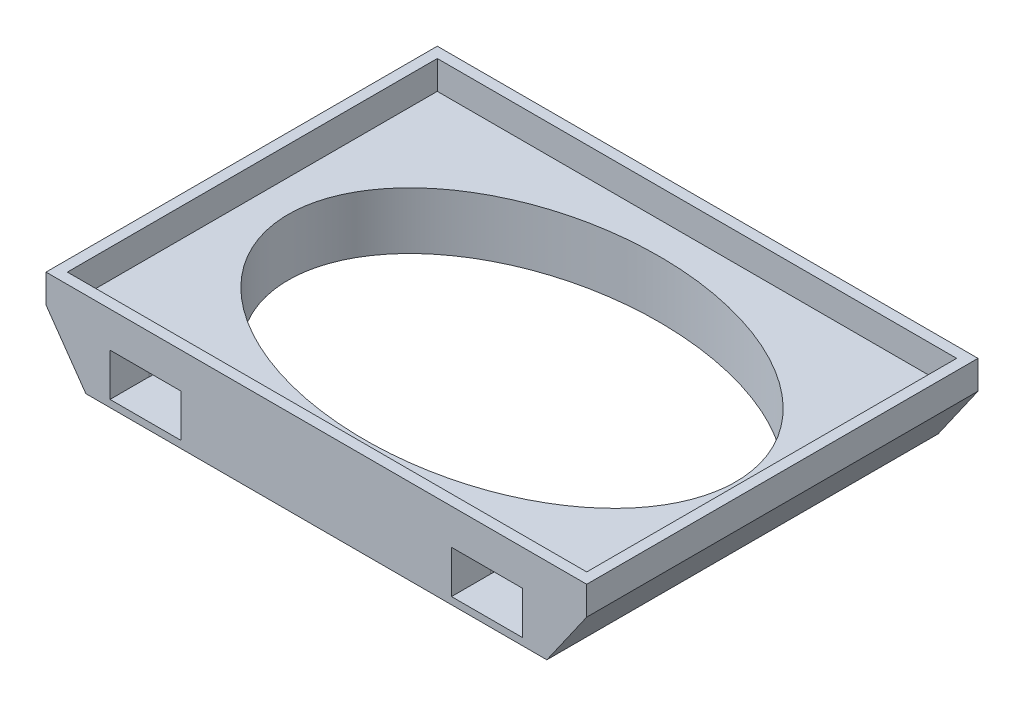
SolidWorks part; units mm, degrees
ref_plane "Front Plane" through (0, 0, 0) normal (0, 0, 1) x (1, 0, 0)
ref_plane "Top Plane" through (0, 0, 0) normal (0, 1, 0) x (1, 0, 0)
ref_plane "Right Plane" through (0, 0, 0) normal (1, 0, 0) x (0, 0, -1)
sketch "Sketch1" plane through (0, 0, 0) normal (0, 1, 0) x (1, 0, 0)
  line L0 (-36.5297, 0) -> (34.0127, 0) construction
  line L1 (0, -19.8975) -> (0, 26.8361) construction
  line L3 (-19, -13.75) -> (19, -13.75)
  line L4 (-19, -13.75) -> (-19, 13.75)
  line L5 (-19, 13.75) -> (19, 13.75)
  line L6 (19, -13.75) -> (19, 13.75)
  dimension "D1" = 27.5
  dimension "D2" = 38
  dimension "D3" = 13.75
  dimension "D4" = 19
extrude "Boss-Extrude1" add sketch "Sketch1" against normal blind 6
sketch "Sketch2" plane through (0, 0, 0) normal (0, 1, 0) x (1, 0, 0)
  line L0 (-19, 13.75) -> (-19, -13.75) construction
  line L1 (-18.25, 13) -> (18.25, 13)
  line L2 (-18.25, 13) -> (-18.25, -13)
  line L3 (-18.25, -13) -> (18.25, -13)
  line L4 (18.25, 13) -> (18.25, -13)
  line L5 (19, -13.75) -> (19, 13.75) construction
  line L6 (19, 13.75) -> (-19, 13.75) construction
  line L7 (-19, -13.75) -> (19, -13.75) construction
  dimension "D1" = 0.75
  dimension "D2" = 0.75
  dimension "D3" = 0.75
  dimension "D4" = 0.75
extrude "Cut-Extrude1" cut sketch "Sketch2" against normal blind 2
sketch "Sketch3" plane through (0, -2, 0) normal (0, 1, 0) x (1, 0, 0)
  line L14 (-19, 13.75) -> (-19, -13.75) construction
  line L15 (-19, -13.75) -> (19, -13.75) construction
  ellipse E0 centre (0, 0) end of major axis (16, -0.498) minor radius 10.7552
  dimension "D1" = 3
  dimension "D2" = 3
extrude "Cut-Extrude2" cut sketch "Sketch3" against normal through all both and the other way through all
sketch "Sketch4" plane through (0, 0, 0) normal (0, 1, 0) x (1, 0, 0)
  line L0 (-25.2485, 0) -> (37.2083, 0) construction
  line L1 (0, -20.0379) -> (0, 20.8772) construction
ref_axis "Axis1" through (0, 0, 20.0379) along (0, 0, -1)
ref_axis "Axis2" through (-25.2485, 0, 0) along (1, 0, 0)
sketch "Sketch7" plane through (0, -6, 0) normal (0, 1, 0) x (1, 0, 0)
  line L5 (-19, -13.75) -> (-9, -13.75)
  line L6 (-19, -13.75) -> (-19, -4.736)
  line L7 (-19, -4.736) -> (-9, -4.736)
  line L8 (-9, -13.75) -> (-9, -4.736)
  line L9 (-19, 13.75) -> (-9, 13.75)
  line L10 (-19, 13.75) -> (-19, 3.75)
  line L11 (-19, 3.75) -> (-9, 3.75)
  line L12 (-9, 13.75) -> (-9, 3.75)
  line L13 (19, 13.75) -> (9, 13.75)
  line L14 (19, 13.75) -> (19, 3.75)
  line L15 (19, 3.75) -> (9, 3.75)
  line L16 (9, 13.75) -> (9, 3.75)
  line L17 (19, -13.75) -> (9, -13.75)
  line L18 (19, -13.75) -> (19, -3.75)
  line L19 (19, -3.75) -> (9, -3.75)
  line L20 (9, -13.75) -> (9, -3.75)
  dimension "D1" = 10
  dimension "D2" = 10
  dimension "D3" = 10
  dimension "D4" = 10
  dimension "D5" = 10
  dimension "D6" = 10
  dimension "D7" = 10
extrude "Cut-Extrude3" [suppressed] cut sketch "Sketch7" along normal blind 1
ref_plane "Plane1" through (0, -4, 0) normal (0, -1, 0) x (-1, 0, 0)
sketch "Sketch8" plane through (0, -4, 0) normal (0, -1, 0) x (-1, 0, 0)
  line L0 (-14.5, 11) -> (-14.5, 23.5627)
  line L1 (-14.5, 23.5627) -> (-9.5, 23.5627)
  line L2 (-9.5, 23.5627) -> (-9.5, 11)
  line L3 (-14.5, 11) -> (-9.5, 11) construction
  line L4 (0, -20.0379) -> (0, 20.8772) construction
  line L5 (25.2485, 0) -> (-37.2083, 0) construction
  line L6 (0, 39.7599) -> (0, -34.6026) construction
  line L7 (-51.5772, 0) -> (38.0826, 0) construction
  line L8 (9.5, 23.5627) -> (9.5, 11)
  line L9 (14.5, 11) -> (14.5, 23.5627)
  line L10 (14.5, 23.5627) -> (9.5, 23.5627)
  line L11 (14.5, -11) -> (14.5, -23.5627)
  line L12 (14.5, -23.5627) -> (9.5, -23.5627)
  line L13 (9.5, -23.5627) -> (9.5, -11)
  line L14 (-9.5, -23.5627) -> (-9.5, -11)
  line L15 (-14.5, -23.5627) -> (-9.5, -23.5627)
  line L16 (-14.5, -11) -> (-14.5, -23.5627)
  arc A1 (14.5, 11) -> (9.5, 11) centre (12, 11) cw
  arc A2 (-14.5, 11) -> (-9.5, 11) centre (-12, 11) ccw
  arc A3 (14.5, -11) -> (9.5, -11) centre (12, -11) ccw
  arc A4 (-14.5, -11) -> (-9.5, -11) centre (-12, -11) cw
  dimension "D1" = 2.5
  dimension "D2" = 90
  dimension "D3" = 12
  dimension "D4" = 11
extrude "Cut-Extrude4" cut sketch "Sketch8" against normal mid plane 3
sketch "Sketch9" plane through (0, 0, 0) normal (0, 0, 1) x (1, 0, 0)
  line L1 (-19, -6) -> (-19, 0) construction
  line L2 (-19, -2) -> (-16.1992, -6)
  line L3 (-19, -6) -> (19, -6) construction
  line L6 (0, 8.1085) -> (0, -16.3772) construction
  line L7 (-16.1992, -6) -> (-19, -6)
  line L9 (-19, -6) -> (-19, -2)
  line L10 (-25.2485, 0) -> (37.2083, 0) construction
  line L11 (16.1992, -6) -> (19, -6)
  line L12 (19, -2) -> (16.1992, -6)
  line L13 (19, -6) -> (19, -2)
  dimension "D1" = 2
  dimension "D2" = 35
extrude "Cut-Extrude5" cut sketch "Sketch9" against normal through all both and the other way through all
